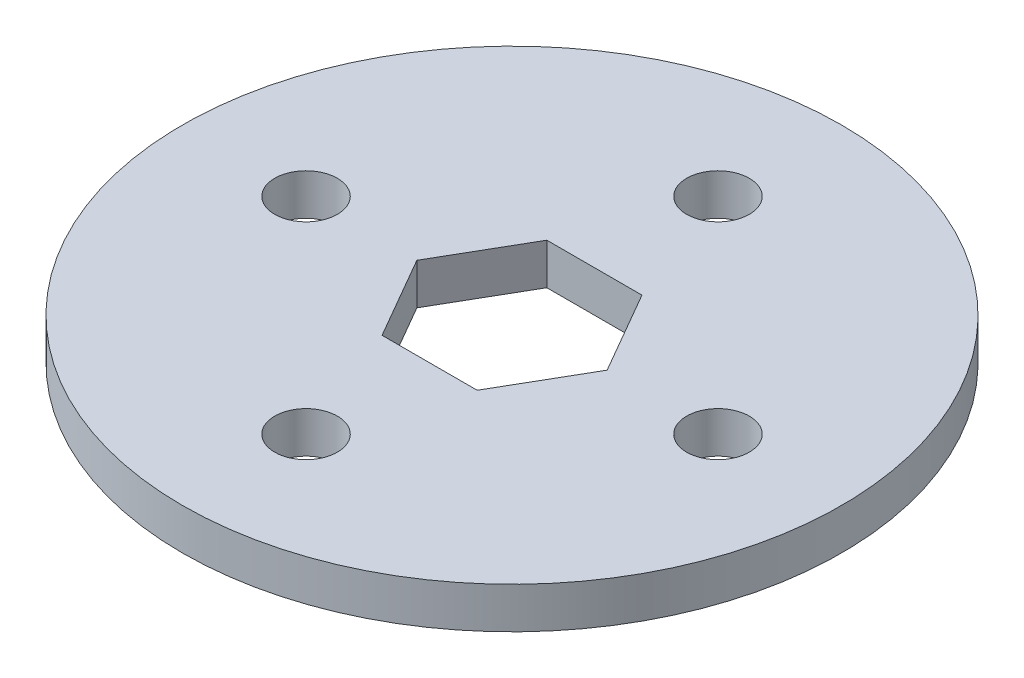
SolidWorks part; units mm, degrees
ref_plane "Front Plane" through (0, 0, 0) normal (0, 0, 1) x (1, 0, 0)
ref_plane "Top Plane" through (0, 0, 0) normal (0, 1, 0) x (1, 0, 0)
ref_plane "Right Plane" through (0, 0, 0) normal (1, 0, 0) x (0, 0, -1)
sketch "Sketch1" plane through (0, 0, 0) normal (0, 1, 0) x (1, 0, 0)
  line L0 (0, 25.4) -> (0, 6.35) construction
  line L1 (-7.3323, 0) -> (-3.6662, -6.35)
  line L2 (-3.6662, -6.35) -> (3.6662, -6.35)
  line L3 (3.6662, -6.35) -> (7.3323, 0)
  line L4 (7.3323, 0) -> (3.6662, 6.35)
  line L5 (3.6662, 6.35) -> (-3.6662, 6.35)
  line L6 (-3.6662, 6.35) -> (-7.3323, 0)
  circle A0 centre (0, 0) radius 25.4
  circle A1 centre (0, 0) radius 6.35 construction
  circle A2 centre (0, 15.875) radius 2.413
  circle A3 centre (15.875, 0) radius 2.413
  circle A4 centre (0, -15.875) radius 2.413
  circle A5 centre (-15.875, 0) radius 2.413
  point P23 (0, 0)
  dimension "D2" = 50.8
  dimension "D3" = 4.826
  dimension "D1" = 12.7
  dimension "D4" = 4
extrude "Boss-Extrude1" add sketch "Sketch1" along normal blind 3.175
